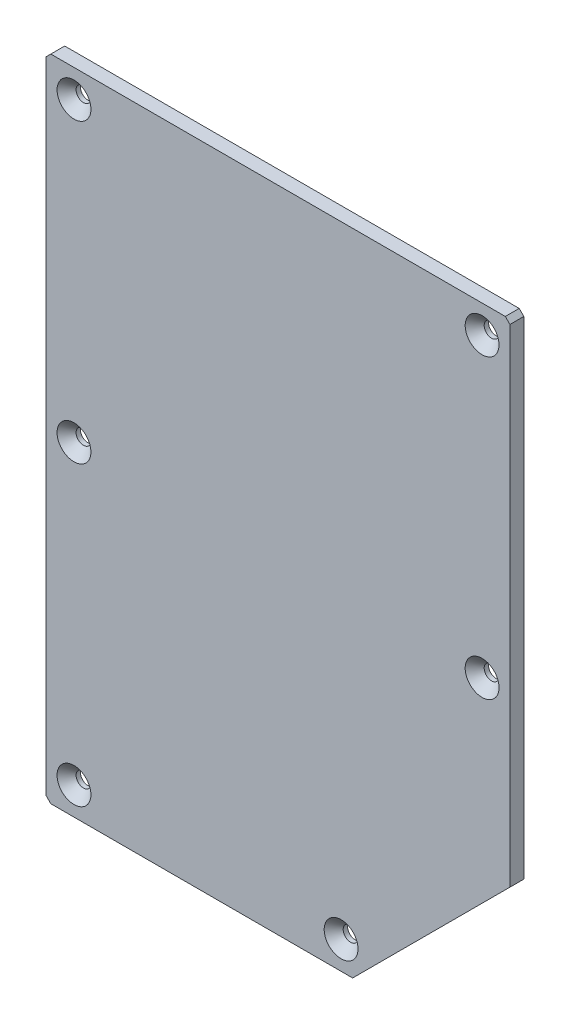
SolidWorks part; units mm, degrees
ref_plane "Front Plane" through (0, 0, 0) normal (0, 0, 1) x (1, 0, 0)
ref_plane "Top Plane" through (0, 0, 0) normal (0, 1, 0) x (1, 0, 0)
ref_plane "Right Plane" through (0, 0, 0) normal (1, 0, 0) x (0, 0, -1)
sketch "Sketch1" plane through (0, 0, 0) normal (0, 0, 1) x (1, 0, 0)
  line L8 (60, -62.4854) -> (60, 42.5997)
  line L9 (60, 42.5997) -> (59, 43.5997)
  line L10 (59, 43.5997) -> (-39, 43.5997)
  line L11 (-39, 43.5997) -> (-40, 42.5997)
  line L12 (-40, 42.5997) -> (-40, -95.4003)
  line L13 (-40, -95.4003) -> (-39, -96.4003)
  line L14 (-39, -96.4003) -> (26.0851, -96.4003)
  line L15 (26.0851, -96.4003) -> (60, -62.4854)
  line L16 (60, -62.4854) -> (60, 42.5997)
  line L17 (60, 42.5997) -> (59, 43.5997)
  line L18 (59, 43.5997) -> (-39, 43.5997)
  line L19 (-39, 43.5997) -> (-40, 42.5997)
  line L20 (-40, 42.5997) -> (-40, -95.4003)
  line L21 (-40, -95.4003) -> (-39, -96.4003)
  line L22 (-39, -96.4003) -> (26.0851, -96.4003)
  line L23 (26.0851, -96.4003) -> (60, -62.4854)
  dimension "D1" = 0
extrude "Boss-Extrude1" add sketch "Sketch1" along normal blind 3
hole_wizard "CSK for M3 Countersunk Flat Head Screw1" positions "3DSketch1" profile "Sketch4" countersink size "M3" standard "ISO" end condition up to next
sketch3d "3DSketch1"
  point P0 (-34, 37.5997, 3)
  point P2 (54, 37.5997, 3)
  point P4 (54, -26.4003, 3)
  point P18 (23.5999, -90.4003, 3)
  point P20 (-34, -90.4003, 3)
  point P22 (-34, -26.4003, 3)
sketch "Sketch4" plane through (-34, 37.5997, 3) normal (1, 0, 0) x (0, -1, 0)
  line L0 (0, 0) -> (0, 3)
  line L1 (0, 3) -> (1.6, 3)
  line L2 (1.6, 3) -> (1.6, 2.05)
  line L3 (1.6, 2.05) -> (3.65, 0)
  line L5 (3.65, 0) -> (0, 0)
  line L6 (-1.6, 2.05) -> (-3.65, 0) construction
  line L11 (0, -6.35) -> (0, 107.95) construction
  dimension "Thru Hole Dia." = 3.2
  dimension "Thru Hole Depth" = 3
  dimension "Near C'Sink Dia." = 7.3
  dimension "Near C'Sink Angle" = 90
